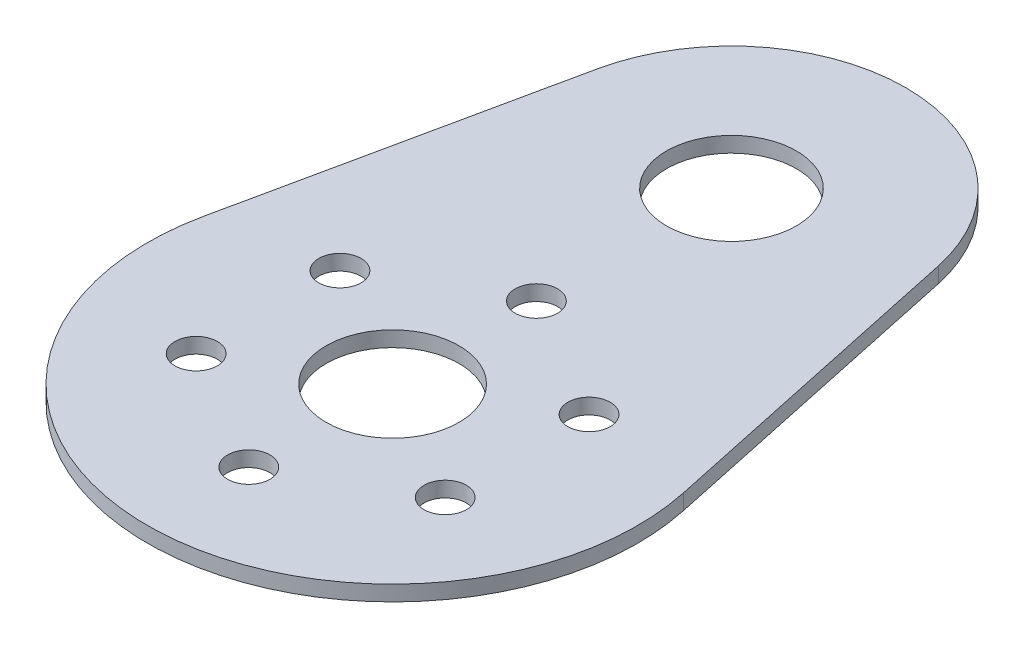
SolidWorks part; units mm, degrees
ref_plane "Front Plane" through (0, 0, 0) normal (0, 0, 1) x (1, 0, 0)
ref_plane "Top Plane" through (0, 0, 0) normal (0, 1, 0) x (1, 0, 0)
ref_plane "Right Plane" through (0, 0, 0) normal (1, 0, 0) x (0, 0, -1)
sketch "Sketch1" plane through (0, 0, 0) normal (0, 1, 0) x (1, 0, 0)
  line L0 (-28.0828, 61.7744) -> (-39.4603, 8.4136)
  line L1 (28.0828, 61.7744) -> (39.4603, 8.4136)
  line L2 (0, 0) -> (0, 55.7867) construction
  arc A0 (-39.4603, 8.4136) -> (39.4603, 8.4136) centre (0, 0) ccw
  circle A1 centre (0, 0) radius 10.9359
  circle A2 centre (0, 23.6743) radius 3.4851
  circle A3 centre (20.5026, 11.8372) radius 3.4851
  circle A4 centre (20.5026, -11.8372) radius 3.4851
  circle A5 centre (0, -23.6743) radius 3.4851
  circle A6 centre (-20.5026, -11.8372) radius 3.4851
  circle A7 centre (-20.5026, 11.8372) radius 3.4851
  circle A8 centre (0, 55.7867) radius 10.6955
  arc A9 (28.0828, 61.7744) -> (-28.0828, 61.7744) centre (0, 55.7867) ccw
  point P1 (0, 55.7867)
  point P18 (0, 0)
  dimension "D1" = 6
extrude "Boss-Extrude1" add sketch "Sketch1" along normal blind 2.54
